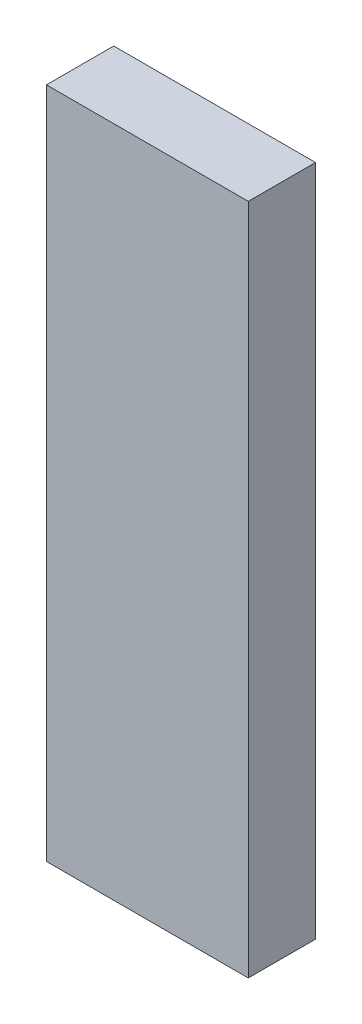
SolidWorks part; units mm, degrees
ref_plane "前视基准面" through (0, 0, 0) normal (0, 0, 1) x (1, 0, 0)
ref_plane "上视基准面" through (0, 0, 0) normal (0, 1, 0) x (1, 0, 0)
ref_plane "右视基准面" through (0, 0, 0) normal (1, 0, 0) x (0, 0, -1)
sketch "草图1" plane through (0, 0, 0) normal (1, 0, 0) x (0, 0, -1)
  line L1 (-10, -100) -> (10, -100)
  line L2 (-10, -100) -> (-10, 100)
  line L3 (-10, 100) -> (10, 100)
  line L4 (10, -100) -> (10, 100)
  line L5 (-10, -100) -> (10, 100) construction
  line L6 (-10, 100) -> (10, -100) construction
  point P0 (0, 0)
extrude "凸台-拉伸1" add sketch "草图1" along normal blind 30 and the other way blind 30
sketch "草图2" plane through (0, 100, 0) normal (0, 1, 0) x (1, 0, 0)
  line L0 (30, 0) -> (-30, 0)
  line L1 (30, 10) -> (30, -10) construction
  line L2 (-30, 10) -> (-30, -10) construction
sketch "草图3" plane through (0, -100, 0) normal (0, -1, 0) x (1, 0, 0)
  line L0 (-30, 0) -> (30, 0)
  line L1 (30, 10) -> (30, -10) construction
ref_axis "基准轴1" through (-30, -100, 0) along (1, 0, 0)
ref_axis "基准轴2" through (30, 100, 0) along (-1, 0, 0)
